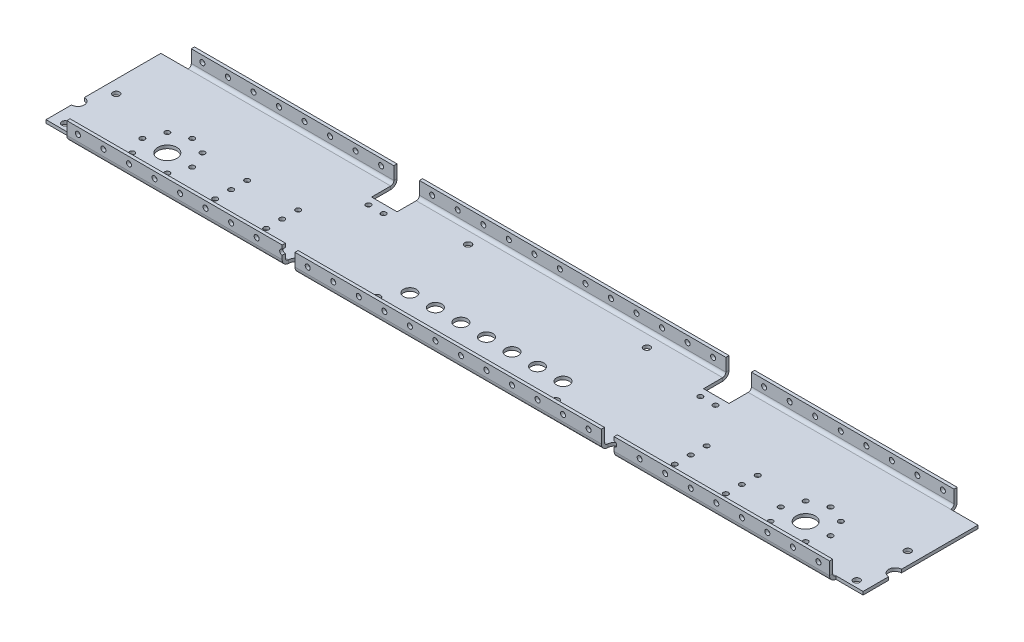
SolidWorks part; units mm, degrees
note: The reader was unsure of these and kept them because the rebuilt part matched: thickness of "Base-Flange1", "Edge-Flange1", "Sheet-Metal1", "Sheet-Metal2", "Sheet-Metal9", "Sheet-Metal10", "Sheet-Metal11", "Sheet-Metal12", "Sheet-Metal13", "Sheet-Metal14", "Sheet-Metal15", "Sheet-Metal16", "Sheet-Metal17", "Sheet-Metal18", "Sheet-Metal19", "Sheet-Metal20"; flange length of "Edge-Flange1".
ref_plane "Front Plane" through (0, 0, 0) normal (0, 0, 1) x (1, 0, 0)
ref_plane "Top Plane" through (0, 0, 0) normal (0, 1, 0) x (1, 0, 0)
ref_plane "Right Plane" through (0, 0, 0) normal (1, 0, 0) x (0, 0, -1)
sketch "Sketch1" plane through (0, 0, 0) normal (0, 1, 0) x (1, 0, 0)
  line L1 (406.4, -63.5) -> (-406.4, -63.5)
  line L2 (406.4, -63.5) -> (406.4, 63.5)
  line L3 (406.4, 63.5) -> (-406.4, 63.5)
  line L4 (-406.4, -63.5) -> (-406.4, 63.5)
  line L5 (406.4, -63.5) -> (-406.4, 63.5) construction
  line L6 (406.4, 63.5) -> (-406.4, -63.5) construction
  point P0 (0, 0)
  dimension "D1" = 127
  dimension "D2" = 812.8
base flange "Base-Flange1" sketch "Sketch1" thickness 3.175 reverse thickness direction no parameters "D1"=1
edge flange "Edge-Flange1" sketch "Sketch23" flange profiles "Sketch23", "Sketch25" flange angle 90 flange length 19.05 flange position material inside bend radius 3.175 thickness 3.175 relief rectangular parameters "D6"=10, "D8"=1
bend "EdgeBend1" bend radius 3.175 bend angle 90 parameters "D5"=1
bend "EdgeBend2" bend radius 3.175 bend angle 90 parameters "D5"=2
sketch "Sketch23" plane through (0, 0, -63.5) normal (0, 0, -1) x (-1, 0, 0)
  line L0 (-406.4, 0) -> (406.4, 0) construction
  line L1 (-406.4, 0) -> (406.4, 0)
  line L2 (-406.4, 0) -> (-406.4, 15.875)
  line L3 (-406.4, 15.875) -> (406.4, 15.875)
  line L4 (406.4, 15.875) -> (406.4, 0)
sketch "Sketch25" plane through (0, 0, 63.5) normal (0, 0, 1) x (1, 0, 0)
  line L0 (-406.4, 0) -> (406.4, 0) construction
  line L1 (-406.4, 0) -> (406.4, 0)
  line L2 (-406.4, 0) -> (-406.4, 15.875)
  line L3 (-406.4, 15.875) -> (406.4, 15.875)
  line L4 (406.4, 15.875) -> (406.4, 0)
hole_wizard "Mounting Holes" positions "Sketch19" profile "Sketch20" hole size "Ø5.0" standard "ANSI Metric" end condition through all
sketch "Sketch19" plane through (342.9, 0, -63.5) normal (0, 0, 1) x (1, 0, 0)
  line L0 (63.5, 9.525) -> (-749.3, 9.525) construction
  line L3 (63.5, 15.875) -> (63.5, 3.175) construction
  point P9 (-736.6, 9.525)
  dimension "D1" = 12.7
sketch "Sketch20" plane through (-393.7, 9.525, -63.5) normal (1, 0, 0) x (0, 1, 0)
  line L0 (0, 0) -> (0, 127)
  line L1 (0, 127) -> (2.5, 127)
  line L2 (2.5, 127) -> (2.5, 0)
  line L5 (2.5, 0) -> (0, 0)
  line L11 (0, -6.35) -> (0, 107.95) construction
  dimension "Thru Hole Dia." = 5
  dimension "Thru Hole Depth" = 127
pattern_linear "LPattern3" count 32 spacing 25.4 along (1, 0, 0) of "Mounting Holes"
sketch "Sketch21" plane through (0, -3.175, 0) normal (0, -1, 0) x (1, 0, 0)
  line L0 (406.4, 0) -> (177.8, 0) construction
  line L1 (406.4, 63.5) -> (-406.4, 63.5) construction
  line L2 (-406.4, -57.15) -> (-379.349, -57.15)
  line L3 (177.8, -38.1) -> (152.4, -38.1)
  line L4 (177.8, -38.1) -> (177.8, -63.5)
  line L5 (177.8, -63.5) -> (152.4, -63.5)
  line L6 (152.4, -38.1) -> (152.4, -63.5)
  line L7 (-177.8, 0) -> (-406.4, 0) construction
  line L8 (-152.4, -63.5) -> (-177.8, -63.5)
  line L9 (-152.4, -63.5) -> (-152.4, -38.1)
  line L10 (-152.4, -38.1) -> (-177.8, -38.1)
  line L11 (-177.8, -63.5) -> (-177.8, -38.1)
  line L12 (-406.4, -57.15) -> (-406.4, 57.15) construction
  line L13 (406.4, 57.15) -> (406.4, -57.15) construction
  line L14 (-406.4, -63.5) -> (406.4, -63.5) construction
  line L16 (-406.4, -57.15) -> (-406.4, -63.5)
  line L17 (-406.4, -63.5) -> (-379.349, -63.5)
  line L18 (-379.349, -57.15) -> (-379.349, -63.5)
  line L19 (-406.4, 57.15) -> (-379.349, 57.15)
  line L20 (-406.4, 57.15) -> (-406.4, 63.5)
  line L21 (-406.4, 63.5) -> (-379.349, 63.5)
  line L22 (-379.349, 57.15) -> (-379.349, 63.5)
  line L23 (379.349, -57.15) -> (379.349, 57.15) construction
  line L24 (406.4, -57.15) -> (379.349, -57.15)
  line L25 (406.4, -57.15) -> (406.4, -63.5)
  line L26 (406.4, -63.5) -> (379.349, -63.5)
  line L27 (379.349, -57.15) -> (379.349, -63.5)
  line L28 (406.4, 57.15) -> (379.349, 57.15)
  line L29 (406.4, 57.15) -> (406.4, 63.5)
  line L30 (406.4, 63.5) -> (379.349, 63.5)
  line L31 (379.349, 57.15) -> (379.349, 63.5)
  dimension "D1" = 228.6
  dimension "D2" = 27.051
  dimension "D3" = 25.4
  dimension "D4" = 25.4
extrude "Cut-Extrude3" cut sketch "Sketch21" against normal through all normal cut yes
sketch "Sketch26" plane through (0, 0, 0) normal (0, 1, 0) x (1, 0, 0)
  line L0 (379.349, -57.15) -> (-379.349, -57.15) construction
  line L1 (152.4, -57.15) -> (152.4, -63.5)
  line L2 (379.349, -63.5) -> (-379.349, -63.5) construction
  line L3 (152.4, -63.5) -> (165.1, -63.5)
  line L4 (165.1, -63.5) -> (165.1, -57.15)
  line L5 (-165.1, -57.15) -> (-165.1, -63.5)
  line L6 (-165.1, -63.5) -> (-152.4, -63.5)
  line L7 (-152.4, -63.5) -> (-152.4, -57.15)
  line L12 (0, 158.0045) -> (0, -158.0045) construction
  line L13 (152.4, -63.5) -> (-152.4, -63.5) construction
  arc A0 (-165.1, -57.15) -> (-152.4, -57.15) centre (-158.75, -57.15) cw
  arc A1 (152.4, -57.15) -> (165.1, -57.15) centre (158.75, -57.15) cw
  point P26 (0, 0)
  point P29 (0, -63.5)
  dimension "D2" = 6.35
  dimension "D1" = 304.8
extrude "Cut-Extrude4" cut sketch "Sketch26" against normal through all both and the other way through all
hole_wizard "80/20 Connection Holes" positions "Sketch27" profile "Sketch28" hole size "Ø6.0" standard "ANSI Metric" end condition through all
sketch "Sketch27" plane through (0, 0, 0) normal (0, 1, 0) x (1, 0, 0)
  line L1 (-393.7, 0) -> (-393.7, -50.8) construction
  line L3 (393.7, -50.8) -> (393.7, 0) construction
  line L4 (406.4, -57.15) -> (406.4, 57.15) construction
  line L5 (393.7, -25.4) -> (406.4, -25.4) construction
  line L7 (-393.7, -25.4) -> (-406.4, -25.4) construction
  line L8 (-406.4, 57.15) -> (-406.4, -57.15) construction
  line L10 (393.7, -50.8) -> (393.7, -57.15) construction
  line L11 (379.349, -57.15) -> (165.1, -57.15) construction
  line L13 (-393.7, -50.8) -> (-393.7, -57.15) construction
  line L14 (-165.1, -57.15) -> (-379.349, -57.15) construction
  line L15 (406.4, -57.15) -> (379.349, -57.15) construction
  point P10 (-393.7, 0)
  point P11 (-393.7, -50.8)
  point P14 (393.7, -50.8)
  point P15 (393.7, 0)
  dimension "D1" = 31.75
  dimension "D5" = 12.7
  dimension "D6" = 50.8
sketch "Sketch28" plane through (-393.7, 0, 0) normal (1, 0, 0) x (0, 0, 1)
  line L0 (0, 0) -> (0, 3.175)
  line L1 (0, 3.175) -> (3.3, 3.175)
  line L2 (3.3, 3.175) -> (3.3, 0)
  line L5 (3.3, 0) -> (0, 0)
  line L11 (0, -6.35) -> (0, 107.95) construction
  dimension "Thru Hole Dia." = 6.6
  dimension "Thru Hole Depth" = 3.175
hole_wizard "Motor Holes" positions "Sketch29" profile "Sketch30" hole size "3/4" standard "ANSI Inch" end condition through all
sketch "Sketch29" plane through (0, 0, 0) normal (0, 1, 0) x (1, 0, 0)
  line L0 (-165.1, -63.5) -> (-379.349, -63.5) construction
  line L1 (-317.5, -25.4) -> (317.5, -25.4) construction
  line L3 (0, 0) -> (0, -25.4) construction
  line L5 (-406.4, 57.15) -> (-406.4, -57.15) construction
  point P0 (-317.5, -25.4)
  point P2 (317.5, -25.4)
  dimension "D1" = 38.1
  dimension "D2" = 88.9
sketch "Sketch30" plane through (-317.5, 0, 25.4) normal (1, 0, 0) x (0, 0, 1)
  line L0 (0, 0) -> (0, 3.175)
  line L1 (0, 3.175) -> (9.525, 3.175)
  line L2 (9.525, 3.175) -> (9.525, 0)
  line L5 (9.525, 0) -> (0, 0)
  line L11 (0, -6.35) -> (0, 107.95) construction
  dimension "Thru Hole Dia." = 19.05
  dimension "Thru Hole Depth" = 3.175
hole_wizard "1/2 (0.5) Diameter Hole1" positions "Sketch31" profile "Sketch32" hole size "1/2" standard "ANSI Inch" end condition through all
sketch "Sketch31" plane through (0, 0, 0) normal (0, 1, 0) x (1, 0, 0)
  line L0 (0, 0) -> (0, -25.4) construction
  line L2 (0, -25.4) -> (-25.4, -25.4) construction
  line L3 (-25.4, -25.4) -> (-50.8, -25.4) construction
  line L4 (-50.8, -25.4) -> (-76.2, -25.4) construction
  line L6 (0, -25.4) -> (25.4, -25.4) construction
  line L7 (25.4, -25.4) -> (50.8, -25.4) construction
  line L8 (50.8, -25.4) -> (76.2, -25.4) construction
  line L9 (152.4, -63.5) -> (-152.4, -63.5) construction
  point P2 (0, -25.4)
  point P8 (-25.4, -25.4)
  point P10 (-50.8, -25.4)
  point P12 (-76.2, -25.4)
  point P17 (25.4, -25.4)
  point P19 (50.8, -25.4)
  point P21 (76.2, -25.4)
  dimension "D1" = 25.4
  dimension "D2" = 38.1
sketch "Sketch32" plane through (76.2, 0, 25.4) normal (1, 0, 0) x (0, 0, 1)
  line L0 (0, 0) -> (0, 3.175)
  line L1 (0, 3.175) -> (6.35, 3.175)
  line L2 (6.35, 3.175) -> (6.35, 0)
  line L5 (6.35, 0) -> (0, 0)
  line L11 (0, -6.35) -> (0, 107.95) construction
  dimension "Thru Hole Dia." = 12.7
  dimension "Thru Hole Depth" = 3.175
sketch "Sketch33" plane through (0, 0, 0) normal (0, 1, 0) x (1, 0, 0)
  line L0 (-406.4, -63.5) -> (-406.4, -25.4) construction
  line L1 (-406.4, 57.15) -> (-406.4, -57.15) construction
  line L2 (-406.4, -19.05) -> (-406.4, -31.75)
  line L3 (406.4, -63.5) -> (406.4, -25.4) construction
  line L4 (406.4, -57.15) -> (406.4, 57.15) construction
  line L5 (406.4, -19.05) -> (406.4, -31.75)
  line L6 (-406.4, -63.5) -> (-379.349, -63.5) construction
  line L7 (379.349, -63.5) -> (406.4, -63.5) construction
  arc A0 (-406.4, -19.05) -> (-406.4, -31.75) centre (-406.4, -25.4) cw
  arc A1 (406.4, -19.05) -> (406.4, -31.75) centre (406.4, -25.4) ccw
  dimension "D1" = 6.35
  dimension "D2" = 38.1
extrude "Cut-Extrude5" cut sketch "Sketch33" against normal through all
hole_wizard "Churrow Holes" positions "Sketch34" profile "Sketch35" hole size "Ø1.0" standard "ANSI Metric" end condition through all
sketch "Sketch34" plane through (0, 0, 0) normal (0, 1, 0) x (1, 0, 0)
  line L0 (-165.1, 50.8) -> (-88.9, 50.8) construction
  line L1 (-88.9, 50.8) -> (-88.9, -63.5) construction
  line L3 (152.4, -63.5) -> (-152.4, -63.5) construction
  line L4 (165.1, 50.8) -> (88.9, 50.8) construction
  line L5 (88.9, 50.8) -> (88.9, -63.5) construction
  line L6 (-88.9, 45.28) -> (88.9, 45.28) construction
  line L8 (-88.9, -45.28) -> (88.9, -45.28) construction
  line L9 (-152.4, 63.5) -> (152.4, 63.5) construction
  line L10 (-165.1, 50.8) -> (-165.1, 38.1) construction
  line L11 (-177.8, 38.1) -> (-152.4, 38.1) construction
  line L13 (165.1, 50.8) -> (165.1, 38.1) construction
  line L14 (152.4, 38.1) -> (177.8, 38.1) construction
  point P16 (-88.9, 45.28)
  point P18 (-88.9, -45.28)
  point P22 (88.9, 45.28)
  point P25 (88.9, -45.28)
  dimension "D1" = 76.2
  dimension "D2" = 18.22
  dimension "D3" = 18.22
sketch "Sketch35" plane through (88.9, 0, 45.28) normal (1, 0, 0) x (0, 0, 1)
  line L0 (0, 0) -> (0, 3.175)
  line L1 (0, 3.175) -> (3.3, 3.175)
  line L2 (3.3, 3.175) -> (3.3, 0)
  line L5 (3.3, 0) -> (0, 0)
  line L11 (0, -6.35) -> (0, 107.95) construction
  dimension "Thru Hole Dia." = 6.6
  dimension "Thru Hole Depth" = 3.175
hole_wizard "80/20 Support Holes" positions "Sketch40" profile "Sketch39" hole size "Ø5.0" standard "ANSI Metric" end condition through all
sketch "Sketch40" plane through (0, 0, 0) normal (0, 1, 0) x (1, 0, 0)
  line L0 (-165.1, 50.8) -> (-165.1, 29.8) construction
  line L2 (-172.6, 29.8) -> (-157.6, 29.8) construction
  line L4 (157.6, 29.8) -> (172.6, 29.8) construction
  line L5 (165.1, 29.8) -> (165.1, 50.8) construction
  point P6 (-172.6, 29.8)
  point P7 (-157.6, 29.8)
  point P10 (-165.1, 29.8)
  point P11 (157.6, 29.8)
  point P12 (172.6, 29.8)
  dimension "D1" = 15
  dimension "D2" = 21
sketch "Sketch39" plane through (172.6, 0, -29.8) normal (1, 0, 0) x (0, 0, 1)
  line L0 (0, 0) -> (0, 3.175)
  line L1 (0, 3.175) -> (2.5, 3.175)
  line L2 (2.5, 3.175) -> (2.5, 0)
  line L5 (2.5, 0) -> (0, 0)
  line L11 (0, -6.35) -> (0, 107.95) construction
  dimension "Thru Hole Dia." = 5
  dimension "Thru Hole Depth" = 3.175
hole_wizard "Motor Gearbox Mounts" positions "Sketch43" profile "Sketch42" hole size "Ø5.0" standard "ANSI Metric"
sketch "Sketch43" plane through (0, 0, 0) normal (0, 1, 0) x (1, 0, 0)
  line L17 (317.5, -25.4) -> (317.5, -0.65) construction
  line L20 (317.5, -0.65) -> (299.9991, -7.8991) construction
  line L21 (299.9991, -7.8991) -> (292.75, -25.4) construction
  line L22 (292.75, -25.4) -> (299.9991, -42.9009) construction
  line L23 (299.9991, -42.9009) -> (317.5, -50.15) construction
  line L24 (317.5, -50.15) -> (335.0009, -42.9009) construction
  line L25 (335.0009, -42.9009) -> (342.25, -25.4) construction
  line L26 (342.25, -25.4) -> (335.0009, -7.8991) construction
  line L27 (335.0009, -7.8991) -> (317.5, -0.65) construction
  line L29 (-317.5, -0.65) -> (-335.0009, -7.8991) construction
  line L30 (-335.0009, -7.8991) -> (-342.25, -25.4) construction
  line L31 (-342.25, -25.4) -> (-335.0009, -42.9009) construction
  line L32 (-335.0009, -42.9009) -> (-317.5, -50.15) construction
  line L33 (-317.5, -50.15) -> (-299.9991, -42.9009) construction
  line L34 (-299.9991, -42.9009) -> (-292.75, -25.4) construction
  line L35 (-292.75, -25.4) -> (-299.9991, -7.8991) construction
  line L36 (-299.9991, -7.8991) -> (-317.5, -0.65) construction
  line L37 (-317.5, -0.65) -> (-317.5, -25.4) construction
  circle A0 centre (317.5, -25.4) radius 22.866 construction
  circle A1 centre (-317.5, -25.4) radius 22.866 construction
  point P64 (317.5, -0.65)
  point P68 (299.9991, -7.8991)
  point P69 (292.75, -25.4)
  point P70 (299.9991, -42.9009)
  point P71 (317.5, -50.15)
  point P72 (335.0009, -42.9009)
  point P73 (342.25, -25.4)
  point P74 (335.0009, -7.8991)
  point P96 (-317.5, -0.65)
  point P97 (-335.0009, -7.8991)
  point P98 (-342.25, -25.4)
  point P99 (-335.0009, -42.9009)
  point P100 (-317.5, -50.15)
  point P101 (-299.9991, -42.9009)
  point P102 (-292.75, -25.4)
  point P103 (-299.9991, -7.8991)
  dimension "D2" = 24.75
sketch "Sketch42" plane through (-299.9991, 0, 7.8991) normal (1, 0, 0) x (0, 0, 1)
  line L0 (0, 0) -> (0, 4.6762)
  line L1 (0, 4.6762) -> (2.5, 3.174)
  line L2 (2.5, 3.174) -> (2.5, 0)
  line L5 (2.5, 0) -> (0, 0)
  line L10 (0, 4.6762) -> (-2.5, 3.174) construction
  line L11 (0, -6.35) -> (0, 107.95) construction
  dimension "Hole Dia." = 5
  dimension "Hole Depth" = 3.174
  dimension "Drill Angle" = 118
hole_wizard "Ø5.0mm Dowel Hole3" positions "Sketch46" profile "Sketch45" hole size "Ø5.0" standard "ANSI Metric"
sketch "Sketch46" plane through (0, 0, 0) normal (0, 1, 0) x (1, 0, 0)
  line L0 (-292.75, -25.4) -> (-254, -25.4) construction
  line L1 (-254, -25.4) -> (-203.2, -25.4) construction
  line L3 (-254, -25.4) -> (-254, -9.525) construction
  line L4 (-254, -9.525) -> (-203.2, -9.525) construction
  line L5 (-203.2, -9.525) -> (-203.2, -25.4) construction
  line L6 (-203.2, -25.4) -> (-203.2, -41.275) construction
  line L7 (-203.2, -41.275) -> (-254, -41.275) construction
  line L8 (-254, -41.275) -> (-254, -25.4) construction
  line L9 (292.75, -25.4) -> (254, -25.4) construction
  line L10 (254, -25.4) -> (203.2, -25.4) construction
  line L11 (203.2, -25.4) -> (203.2, -9.525) construction
  line L12 (203.2, -9.525) -> (254, -9.525) construction
  line L13 (254, -9.525) -> (254, -25.4) construction
  line L14 (254, -25.4) -> (254, -41.275) construction
  line L15 (254, -41.275) -> (203.2, -41.275) construction
  line L16 (203.2, -41.275) -> (203.2, -25.4) construction
  point P2 (-254, -25.4)
  point P5 (-203.2, -25.4)
  point P9 (-254, -9.525)
  point P11 (-203.2, -9.525)
  point P14 (-203.2, -41.275)
  point P15 (-254, -41.275)
  point P33 (254, -25.4)
  point P35 (203.2, -25.4)
  point P36 (203.2, -9.525)
  point P37 (254, -9.525)
  point P39 (254, -41.275)
  point P40 (203.2, -41.275)
  dimension "D1" = 38.75
  dimension "D2" = 15.875
  dimension "D3" = 50.8
sketch "Sketch45" plane through (203.2, 0, 41.275) normal (1, 0, 0) x (0, 0, 1)
  line L0 (0, 0) -> (0, 4.6762)
  line L1 (0, 4.6762) -> (2.5, 3.174)
  line L2 (2.5, 3.174) -> (2.5, 0)
  line L5 (2.5, 0) -> (0, 0)
  line L10 (0, 4.6762) -> (-2.5, 3.174) construction
  line L11 (0, -6.35) -> (0, 107.95) construction
  dimension "Hole Dia." = 5
  dimension "Hole Depth" = 3.174
  dimension "Drill Angle" = 118
sketch "Bend-Lines1" [suppressed] plane through (0, 0, 0) normal (0, 1, 0) x (1, 0, 0)
sketch "Bounding-Box1" [suppressed] plane through (0, 0, 0) normal (0, 1, 0) x (1, 0, 0)
sheet metal parameters "Sheet-Metal1" thickness 3.175 parameters "D1"=1, "D7"=3
flat pattern "Flat-Pattern1" [suppressed]
sketch "Bend-Lines2" plane through (0, 0, 0) normal (0, 1, 0) x (1, 0, 0)
sketch3d "Bounding-Box2" [suppressed]
  line L0 (-77.3309, 406.4, 0) -> (-77.3309, -406.4, 0) construction
  line L1 (77.3309, 406.4, 0) -> (77.3309, -406.4, 0) construction
  line L2 (-77.3309, 406.4, 0) -> (77.3309, 406.4, 0) construction
  line L3 (-77.3309, -406.4, 0) -> (77.3309, -406.4, 0) construction
sheet metal parameters "Sheet-Metal2" thickness 3.175 parameters "D1"=1, "D7"=3
flat pattern "Flat-Pattern1"
sketch "Bend-Lines2" plane through (0, 0, 0) normal (0, 1, 0) x (1, 0, 0)
  line L4 (-406.4, -60.8905) -> (406.4, -60.8905) construction
  line L5 (406.4, 60.8905) -> (-406.4, 60.8905) construction
  line L6 (-406.4, -60.8905) -> (406.4, -60.8905) construction
  line L7 (406.4, 60.8905) -> (-406.4, 60.8905) construction
  point P0 (-60.8905, 406.4)
  point P1 (-60.8905, -406.4)
  point P2 (60.8905, -406.4)
  point P3 (60.8905, 406.4)
sketch3d "Bounding-Box2" [suppressed]
  line L0 (406.4, -77.3309, 0) -> (-406.4, -77.3309, 0) construction
  line L1 (406.4, 77.3309, 0) -> (-406.4, 77.3309, 0) construction
  line L2 (406.4, -77.3309, 0) -> (406.4, 77.3309, 0) construction
  line L3 (-406.4, -77.3309, 0) -> (-406.4, 77.3309, 0) construction
bend of the flat pattern "Flatten-<EdgeBend1>1"
bend of the flat pattern "Flatten-<EdgeBend2>1"
sheet metal parameters "Sheet-Metal9" thickness 3.175 parameters "D1"=1, "D7"=3
flat pattern "Flat-Pattern1" [suppressed]
sketch "Bend-Lines2" plane through (0, 0, 0) normal (0, 1, 0) x (1, 0, 0)
  line L0 (-60.8905, 406.4) -> (-60.8905, -406.4) construction
  line L1 (60.8905, -406.4) -> (60.8905, 406.4) construction
  line L2 (-60.8905, 406.4) -> (-60.8905, -406.4) construction
  line L3 (60.8905, -406.4) -> (60.8905, 406.4) construction
sketch3d "Bounding-Box2" [suppressed]
  line L0 (-77.3309, 406.4, 0) -> (-77.3309, -406.4, 0) construction
  line L1 (77.3309, 406.4, 0) -> (77.3309, -406.4, 0) construction
  line L2 (-77.3309, 406.4, 0) -> (77.3309, 406.4, 0) construction
  line L3 (-77.3309, -406.4, 0) -> (77.3309, -406.4, 0) construction
bend of the flat pattern "Flatten-<EdgeBend2>2"
bend of the flat pattern "Flatten-<EdgeBend1>2"
sheet metal parameters "Sheet-Metal10" thickness 3.175 parameters "D1"=1, "D7"=3
flat pattern "Flat-Pattern1"
sketch "Bend-Lines2" plane through (0, 0, 0) normal (0, 1, 0) x (1, 0, 0)
  line L4 (-406.4, -60.8905) -> (406.4, -60.8905) construction
  line L5 (406.4, 60.8905) -> (-406.4, 60.8905) construction
  line L6 (-406.4, -60.8905) -> (406.4, -60.8905) construction
  line L7 (406.4, 60.8905) -> (-406.4, 60.8905) construction
sketch3d "Bounding-Box2" [suppressed]
  line L0 (406.4, -77.3309, 0) -> (-406.4, -77.3309, 0) construction
  line L1 (406.4, 77.3309, 0) -> (-406.4, 77.3309, 0) construction
  line L2 (406.4, -77.3309, 0) -> (406.4, 77.3309, 0) construction
  line L3 (-406.4, -77.3309, 0) -> (-406.4, 77.3309, 0) construction
bend of the flat pattern "Flatten-<EdgeBend2>3"
bend of the flat pattern "Flatten-<EdgeBend1>3"
sheet metal parameters "Sheet-Metal11" thickness 3.175 parameters "D1"=1, "D7"=3
flat pattern "Flat-Pattern1"
sketch "Bend-Lines2" plane through (0, 0, 0) normal (0, 1, 0) x (1, 0, 0)
  line L6 (-406.4, -60.8905) -> (406.4, -60.8905) construction
  line L7 (406.4, 60.8905) -> (-406.4, 60.8905) construction
  line L8 (-406.4, -60.8905) -> (406.4, -60.8905) construction
  line L9 (406.4, 60.8905) -> (177.8, 60.8905) construction
  line L10 (152.4, 60.8905) -> (-152.4, 60.8905) construction
  line L11 (-177.8, 60.8905) -> (-406.4, 60.8905) construction
  point P0 (-60.8905, 406.4)
  point P1 (-60.8905, -406.4)
  point P2 (60.8905, 177.8)
  point P3 (60.8905, 406.4)
sketch3d "Bounding-Box2" [suppressed]
  line L0 (406.4, -77.3309, 0) -> (-406.4, -77.3309, 0) construction
  line L1 (406.4, 77.3309, 0) -> (-406.4, 77.3309, 0) construction
  line L2 (406.4, -77.3309, 0) -> (406.4, 77.3309, 0) construction
  line L3 (-406.4, -77.3309, 0) -> (-406.4, 77.3309, 0) construction
bend of the flat pattern "Flatten-<EdgeBend2>4"
bend of the flat pattern "Flatten-<EdgeBend1>4"
sheet metal parameters "Sheet-Metal12" thickness 3.175 parameters "D1"=1, "D7"=3
flat pattern "Flat-Pattern1"
sketch "Bend-Lines2" plane through (0, 0, 0) normal (0, 1, 0) x (1, 0, 0)
  line L0 (-406.4, -60.8905) -> (-203.2, -60.8905) construction
  line L1 (-190.5, -60.8905) -> (190.5, -60.8905) construction
  line L6 (203.2, -60.8905) -> (406.4, -60.8905) construction
  line L7 (406.4, 60.8905) -> (-406.4, 60.8905) construction
  line L8 (203.2, -60.8905) -> (406.4, -60.8905) construction
  line L9 (406.4, 60.8905) -> (177.8, 60.8905) construction
  line L10 (152.4, 60.8905) -> (-152.4, 60.8905) construction
  line L11 (-177.8, 60.8905) -> (-406.4, 60.8905) construction
sketch3d "Bounding-Box2" [suppressed]
  line L0 (406.4, -77.3309, 0) -> (-406.4, -77.3309, 0) construction
  line L1 (406.4, 77.3309, 0) -> (-406.4, 77.3309, 0) construction
  line L2 (406.4, -77.3309, 0) -> (406.4, 77.3309, 0) construction
  line L3 (-406.4, -77.3309, 0) -> (-406.4, 77.3309, 0) construction
bend of the flat pattern "Flatten-<EdgeBend2>4"
bend of the flat pattern "Flatten-<EdgeBend1>4"
sheet metal parameters "Sheet-Metal13" thickness 3.175 parameters "D1"=1, "D7"=3
flat pattern "Flat-Pattern1"
sketch "Bend-Lines2" plane through (0, 0, 0) normal (0, 1, 0) x (1, 0, 0)
  line L0 (-406.4, -60.8905) -> (-203.2, -60.8905) construction
  line L1 (-190.5, -60.8905) -> (190.5, -60.8905) construction
  line L6 (203.2, -60.8905) -> (406.4, -60.8905) construction
  line L7 (406.4, 60.8905) -> (-406.4, 60.8905) construction
  line L8 (203.2, -60.8905) -> (406.4, -60.8905) construction
  line L9 (406.4, 60.8905) -> (177.8, 60.8905) construction
  line L10 (152.4, 60.8905) -> (-152.4, 60.8905) construction
  line L11 (-177.8, 60.8905) -> (-406.4, 60.8905) construction
sketch3d "Bounding-Box2" [suppressed]
  line L0 (406.4, -77.3309, 0) -> (-406.4, -77.3309, 0) construction
  line L1 (406.4, 77.3309, 0) -> (-406.4, 77.3309, 0) construction
  line L2 (406.4, -77.3309, 0) -> (406.4, 77.3309, 0) construction
  line L3 (-406.4, -77.3309, 0) -> (-406.4, 77.3309, 0) construction
bend of the flat pattern "Flatten-<EdgeBend2>4"
bend of the flat pattern "Flatten-<EdgeBend1>4"
sheet metal parameters "Sheet-Metal14" thickness 3.175 parameters "D1"=1, "D7"=3
flat pattern "Flat-Pattern1"
sketch "Bend-Lines2" plane through (0, 0, 0) normal (0, 1, 0) x (1, 0, 0)
  line L0 (-406.4, -60.8905) -> (-203.2, -60.8905) construction
  line L1 (-190.5, -60.8905) -> (190.5, -60.8905) construction
  line L6 (203.2, -60.8905) -> (406.4, -60.8905) construction
  line L7 (406.4, 60.8905) -> (-406.4, 60.8905) construction
  line L8 (203.2, -60.8905) -> (406.4, -60.8905) construction
  line L9 (406.4, 60.8905) -> (177.8, 60.8905) construction
  line L10 (152.4, 60.8905) -> (-152.4, 60.8905) construction
  line L11 (-177.8, 60.8905) -> (-406.4, 60.8905) construction
sketch3d "Bounding-Box2" [suppressed]
  line L0 (406.4, -77.3309, 0) -> (-406.4, -77.3309, 0) construction
  line L1 (406.4, 77.3309, 0) -> (-406.4, 77.3309, 0) construction
  line L2 (406.4, -77.3309, 0) -> (406.4, 77.3309, 0) construction
  line L3 (-406.4, -77.3309, 0) -> (-406.4, 77.3309, 0) construction
bend of the flat pattern "Flatten-<EdgeBend2>4"
bend of the flat pattern "Flatten-<EdgeBend1>4"
sheet metal parameters "Sheet-Metal15" thickness 3.175 parameters "D1"=1, "D7"=3
flat pattern "Flat-Pattern1"
sketch "Bend-Lines2" plane through (0, 0, 0) normal (0, 1, 0) x (1, 0, 0)
  line L0 (-406.4, -60.8905) -> (-203.2, -60.8905) construction
  line L1 (-190.5, -60.8905) -> (190.5, -60.8905) construction
  line L6 (203.2, -60.8905) -> (406.4, -60.8905) construction
  line L7 (406.4, 60.8905) -> (-406.4, 60.8905) construction
  line L8 (203.2, -60.8905) -> (406.4, -60.8905) construction
  line L9 (406.4, 60.8905) -> (177.8, 60.8905) construction
  line L10 (152.4, 60.8905) -> (-152.4, 60.8905) construction
  line L11 (-177.8, 60.8905) -> (-406.4, 60.8905) construction
sketch3d "Bounding-Box2" [suppressed]
  line L0 (406.4, -77.3309, 0) -> (-406.4, -77.3309, 0) construction
  line L1 (406.4, 77.3309, 0) -> (-406.4, 77.3309, 0) construction
  line L2 (406.4, -77.3309, 0) -> (406.4, 77.3309, 0) construction
  line L3 (-406.4, -77.3309, 0) -> (-406.4, 77.3309, 0) construction
bend of the flat pattern "Flatten-<EdgeBend2>4"
bend of the flat pattern "Flatten-<EdgeBend1>4"
sheet metal parameters "Sheet-Metal16" thickness 3.175 parameters "D1"=1, "D7"=3
flat pattern "Flat-Pattern1"
sketch "Bend-Lines2" plane through (0, 0, 0) normal (0, 1, 0) x (1, 0, 0)
  line L0 (-190.5, -60.8905) -> (190.5, -60.8905) construction
  line L1 (203.2, -60.8905) -> (406.4, -60.8905) construction
  line L6 (-406.4, -60.8905) -> (-203.2, -60.8905) construction
  line L7 (406.4, 60.8905) -> (-406.4, 60.8905) construction
  line L8 (-406.4, -60.8905) -> (-203.2, -60.8905) construction
  line L9 (406.4, 60.8905) -> (177.8, 60.8905) construction
  line L10 (152.4, 60.8905) -> (-152.4, 60.8905) construction
  line L11 (-177.8, 60.8905) -> (-406.4, 60.8905) construction
sketch3d "Bounding-Box2" [suppressed]
  line L0 (406.4, -77.3309, 0) -> (-406.4, -77.3309, 0) construction
  line L1 (406.4, 77.3309, 0) -> (-406.4, 77.3309, 0) construction
  line L2 (406.4, -77.3309, 0) -> (406.4, 77.3309, 0) construction
  line L3 (-406.4, -77.3309, 0) -> (-406.4, 77.3309, 0) construction
bend of the flat pattern "Flatten-<EdgeBend2>4"
bend of the flat pattern "Flatten-<EdgeBend1>4"
sheet metal parameters "Sheet-Metal17" thickness 3.175 parameters "D1"=1, "D7"=3
flat pattern "Flat-Pattern1"
sketch "Bend-Lines2" plane through (0, 0, 0) normal (0, 1, 0) x (1, 0, 0)
  line L0 (-190.5, -60.8905) -> (190.5, -60.8905) construction
  line L1 (203.2, -60.8905) -> (406.4, -60.8905) construction
  line L6 (-406.4, -60.8905) -> (-203.2, -60.8905) construction
  line L7 (406.4, 60.8905) -> (-406.4, 60.8905) construction
  line L8 (-406.4, -60.8905) -> (-203.2, -60.8905) construction
  line L9 (406.4, 60.8905) -> (177.8, 60.8905) construction
  line L10 (152.4, 60.8905) -> (-152.4, 60.8905) construction
  line L11 (-177.8, 60.8905) -> (-406.4, 60.8905) construction
sketch3d "Bounding-Box2" [suppressed]
  line L0 (406.4, -77.3309, 0) -> (-406.4, -77.3309, 0) construction
  line L1 (406.4, 77.3309, 0) -> (-406.4, 77.3309, 0) construction
  line L2 (406.4, -77.3309, 0) -> (406.4, 77.3309, 0) construction
  line L3 (-406.4, -77.3309, 0) -> (-406.4, 77.3309, 0) construction
bend of the flat pattern "Flatten-<EdgeBend2>4"
bend of the flat pattern "Flatten-<EdgeBend1>4"
sheet metal parameters "Sheet-Metal18" thickness 3.175 parameters "D1"=1, "D7"=3
flat pattern "Flat-Pattern1"
sketch "Bend-Lines2" plane through (0, 0, 0) normal (0, 1, 0) x (1, 0, 0)
  line L0 (-152.4, -60.8905) -> (152.4, -60.8905) construction
  line L1 (165.1, -60.8905) -> (379.349, -60.8905) construction
  line L6 (-379.349, -60.8905) -> (-165.1, -60.8905) construction
  line L7 (379.349, 60.8905) -> (-379.349, 60.8905) construction
  line L8 (-379.349, -60.8905) -> (-165.1, -60.8905) construction
  line L9 (379.349, 60.8905) -> (177.8, 60.8905) construction
  line L10 (152.4, 60.8905) -> (-152.4, 60.8905) construction
  line L11 (-177.8, 60.8905) -> (-379.349, 60.8905) construction
sketch3d "Bounding-Box2" [suppressed]
  line L0 (406.4, -77.3309, 0) -> (-406.4, -77.3309, 0) construction
  line L1 (406.4, 77.3309, 0) -> (-406.4, 77.3309, 0) construction
  line L2 (406.4, -77.3309, 0) -> (406.4, 77.3309, 0) construction
  line L3 (-406.4, -77.3309, 0) -> (-406.4, 77.3309, 0) construction
bend of the flat pattern "Flatten-<EdgeBend2>4"
bend of the flat pattern "Flatten-<EdgeBend1>4"
sheet metal parameters "Sheet-Metal19" thickness 3.175 parameters "D1"=1, "D7"=3
flat pattern "Flat-Pattern1"
sketch "Bend-Lines2" plane through (0, 0, 0) normal (0, 1, 0) x (1, 0, 0)
  line L0 (-152.4, -60.8905) -> (152.4, -60.8905) construction
  line L1 (165.1, -60.8905) -> (379.349, -60.8905) construction
  line L6 (-379.349, -60.8905) -> (-165.1, -60.8905) construction
  line L7 (379.349, 60.8905) -> (-379.349, 60.8905) construction
  line L8 (-379.349, -60.8905) -> (-165.1, -60.8905) construction
  line L9 (379.349, 60.8905) -> (177.8, 60.8905) construction
  line L10 (152.4, 60.8905) -> (-152.4, 60.8905) construction
  line L11 (-177.8, 60.8905) -> (-379.349, 60.8905) construction
sketch3d "Bounding-Box2" [suppressed]
  line L0 (406.4, -77.3309, 0) -> (-406.4, -77.3309, 0) construction
  line L1 (406.4, 77.3309, 0) -> (-406.4, 77.3309, 0) construction
  line L2 (406.4, -77.3309, 0) -> (406.4, 77.3309, 0) construction
  line L3 (-406.4, -77.3309, 0) -> (-406.4, 77.3309, 0) construction
bend of the flat pattern "Flatten-<EdgeBend2>4"
bend of the flat pattern "Flatten-<EdgeBend1>4"
sheet metal parameters "Sheet-Metal20" thickness 3.175 parameters "D1"=1, "D7"=3
flat pattern "Flat-Pattern1"
sketch "Bend-Lines2" plane through (0, 0, 0) normal (0, 1, 0) x (1, 0, 0)
  line L0 (-152.4, -60.8905) -> (152.4, -60.8905) construction
  line L1 (165.1, -60.8905) -> (379.349, -60.8905) construction
  line L6 (-379.349, -60.8905) -> (-165.1, -60.8905) construction
  line L7 (379.349, 60.8905) -> (-379.349, 60.8905) construction
  line L8 (-379.349, -60.8905) -> (-165.1, -60.8905) construction
  line L9 (379.349, 60.8905) -> (177.8, 60.8905) construction
  line L10 (152.4, 60.8905) -> (-152.4, 60.8905) construction
  line L11 (-177.8, 60.8905) -> (-379.349, 60.8905) construction
sketch3d "Bounding-Box2" [suppressed]
  line L0 (406.4, -77.3309, 0) -> (-406.4, -77.3309, 0) construction
  line L1 (406.4, 77.3309, 0) -> (-406.4, 77.3309, 0) construction
  line L2 (406.4, -77.3309, 0) -> (406.4, 77.3309, 0) construction
  line L3 (-406.4, -77.3309, 0) -> (-406.4, 77.3309, 0) construction
bend of the flat pattern "Flatten-<EdgeBend2>4"
bend of the flat pattern "Flatten-<EdgeBend1>4"
